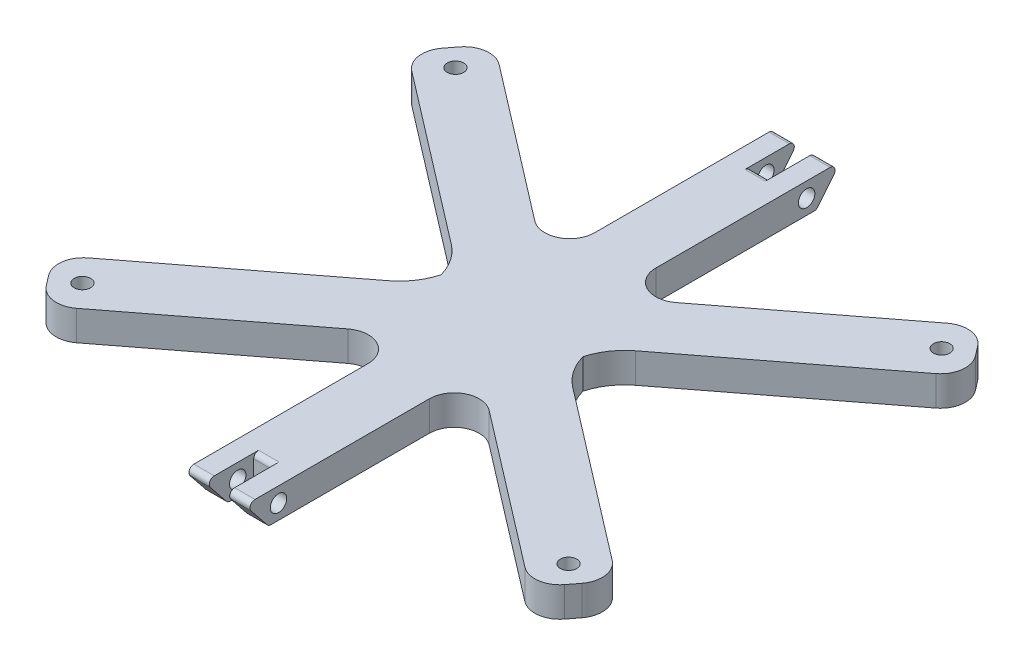
SolidWorks part; units mm, degrees
ref_plane "Front Plane" through (0, 0, 0) normal (0, 0, 1) x (1, 0, 0)
ref_plane "Top Plane" through (0, 0, 0) normal (0, 1, 0) x (1, 0, 0)
ref_plane "Right Plane" through (0, 0, 0) normal (1, 0, 0) x (0, 0, -1)
sketch "Sketch1" plane through (0, 0, 0) normal (0, 1, 0) x (1, 0, 0)
  circle A0 centre (0, 0) radius 14
  dimension "D1" = 28
extrude "Boss-Extrude1" add sketch "Sketch1" along normal blind 6
sketch "Sketch2" plane through (0, 0, 0) normal (0, 1, 0) x (1, 0, 0)
  line L0 (-13.7435, 2.6678) -> (-56.5628, 35.5242)
  line L1 (0.2695, -0.2068) -> (-63.7589, 48.924) construction
  line L2 (-48.9532, 45.4411) -> (-6.134, 12.5847)
  line L3 (0, 37.6664) -> (0, -25.0328) construction
  line L4 (-48.9532, 45.4411) -> (-56.5628, 35.5242)
  circle A0 centre (0, 0) radius 14 construction
  arc A1 (-6.134, 12.5847) -> (-13.7435, 2.6678) centre (0, 0) ccw
  point P9 (-52.758, 40.4826)
  dimension "D1" = 66.5
  dimension "D2" = 52.5
  dimension "D3" = 12.5
extrude "Boss-Extrude2" add sketch "Sketch2" along normal up to surface (6 mm away) up to face at (0, 6, 14)
mirror "Mirror1" about plane through (0, 0, 0) normal (1, 0, 0) of "Boss-Extrude2"
mirror "Mirror2" about plane through (0, 0, 0) normal (0, 0, 1) of "Mirror1", "Boss-Extrude2"
sketch "Sketch4" plane through (0, 6, 0) normal (0, 1, 0) x (1, 0, 0)
  line L0 (0, 65.599) -> (0, -44.8835) construction
  line L1 (-6.134, 59.8) -> (-6.134, 12.5847)
  line L2 (-6.134, 59.8) -> (6.134, 59.8)
  line L3 (6.134, 59.8) -> (6.134, 12.5847)
  arc A2 (6.134, 12.5847) -> (-6.134, 12.5847) centre (0, 0) ccw construction
  arc A3 (6.134, 12.5847) -> (-6.134, 12.5847) centre (0, 0) ccw
  point P8 (0, 59.8)
  dimension "D2" = 59.8
extrude "Boss-Extrude4" add sketch "Sketch4" against normal up to surface (6 mm away) up to face at (0, 0, 0)
mirror "Mirror6" about plane through (0, 0, 0) normal (0, 0, 1) of "Boss-Extrude4"
fillet "Fillet4" radius 5 4 edges at (6.134, 3, 12.5847) (-6.134, 3, 12.5847) (6.134, 3, -12.5847) (-6.134, 3, -12.5847)
fillet "Fillet5" radius 12 4 edges at (-13.7435, 3, 2.6678) (-13.7435, 3, -2.6678) (13.7435, 3, 2.6678) (13.7435, 3, -2.6678)
sketch "Sketch3" plane through (0, 6, 0) normal (0, 1, 0) x (1, 0, 0)
  line L1 (-48.9532, 45.4411) -> (-56.5628, 35.5242) construction
  circle A0 centre (-48.7912, 37.4388) radius 1.65
  dimension "D1" = 3.3
  dimension "D2" = 61.5
extrude "Cut-Extrude1" cut sketch "Sketch3" against normal through all
mirror "Mirror3" about plane through (0, 0, 0) normal (1, 0, 0) of "Cut-Extrude1"
mirror "Mirror4" about plane through (0, 0, 0) normal (0, 0, 1) of "Mirror3", "Cut-Extrude1"
sketch "Sketch5" plane through (0, 6, 0) normal (0, 1, 0) x (1, 0, 0)
  line L0 (6.134, 59.8) -> (-6.134, 59.8) construction
  circle A0 centre (0, 54.8) radius 1.65
  dimension "D1" = 3.3
  dimension "D2" = 5
extrude "Cut-Extrude2" [suppressed] cut sketch "Sketch5" against normal through all
mirror "Mirror7" [suppressed] about plane through (0, 0, 0) normal (0, 0, 1)
fillet "Fillet3" radius 5 8 edges at (48.9532, 3, 45.4411) (56.5628, 3, 35.5242) (56.5628, 3, -35.5242) (48.9532, 3, -45.4411) (-48.9532, 3, -45.4411) (-56.5628, 3, -35.5242) (-56.5628, 3, 35.5242) (-48.9532, 3, 45.4411)
sketch "Sketch12" plane through (-6.134, 0, 0) normal (-1, 0, 0) x (0, 0, 1)
  line L0 (-59.8, 6) -> (-54.981, 0)
  line L1 (-22.7237, 0) -> (-59.8, 0) construction
  line L2 (-54.981, 0) -> (-59.8, 0)
  line L3 (-59.8, 0) -> (-59.8, 6)
  dimension "D1" = 128.77
extrude "Cut-Extrude8" cut sketch "Sketch12" against normal blind 14
sketch "Sketch13" plane through (-6.134, 0, 0) normal (-1, 0, 0) x (0, 0, 1)
  circle A0 centre (-53, 3) radius 1.65
  dimension "D2" = 3.3
  dimension "D1" = 53
extrude "Cut-Extrude9" cut sketch "Sketch13" against normal blind 14
sketch "Sketch14" plane through (0, 6, 0) normal (0, 1, 0) x (1, 0, 0)
  line L0 (-2.05, 59.8) -> (2.05, 59.8)
  line L1 (6.134, 59.8) -> (-6.134, 59.8) construction
  line L2 (2.05, 59.8) -> (2.05, 49.8)
  line L3 (2.05, 49.8) -> (-2.05, 49.8)
  line L4 (-2.05, 49.8) -> (-2.05, 59.8)
  point P4 (0, 49.8)
  dimension "D1" = 10
  dimension "D2" = 4.1
extrude "Cut-Extrude10" cut sketch "Sketch14" against normal blind 14
fillet "Fillet6" radius 1 6 edges at (-4.092, 6, -59.8) (4.092, 6, -59.8) (-4.092, 0, -54.981) (4.092, 0, -54.981) (0, 0, -49.8) (0, 6, -49.8)
mirror "Mirror8" about plane through (0, 0, 0) normal (0, 0, 1) of "Fillet6", "Cut-Extrude10", "Cut-Extrude9", "Cut-Extrude8"
